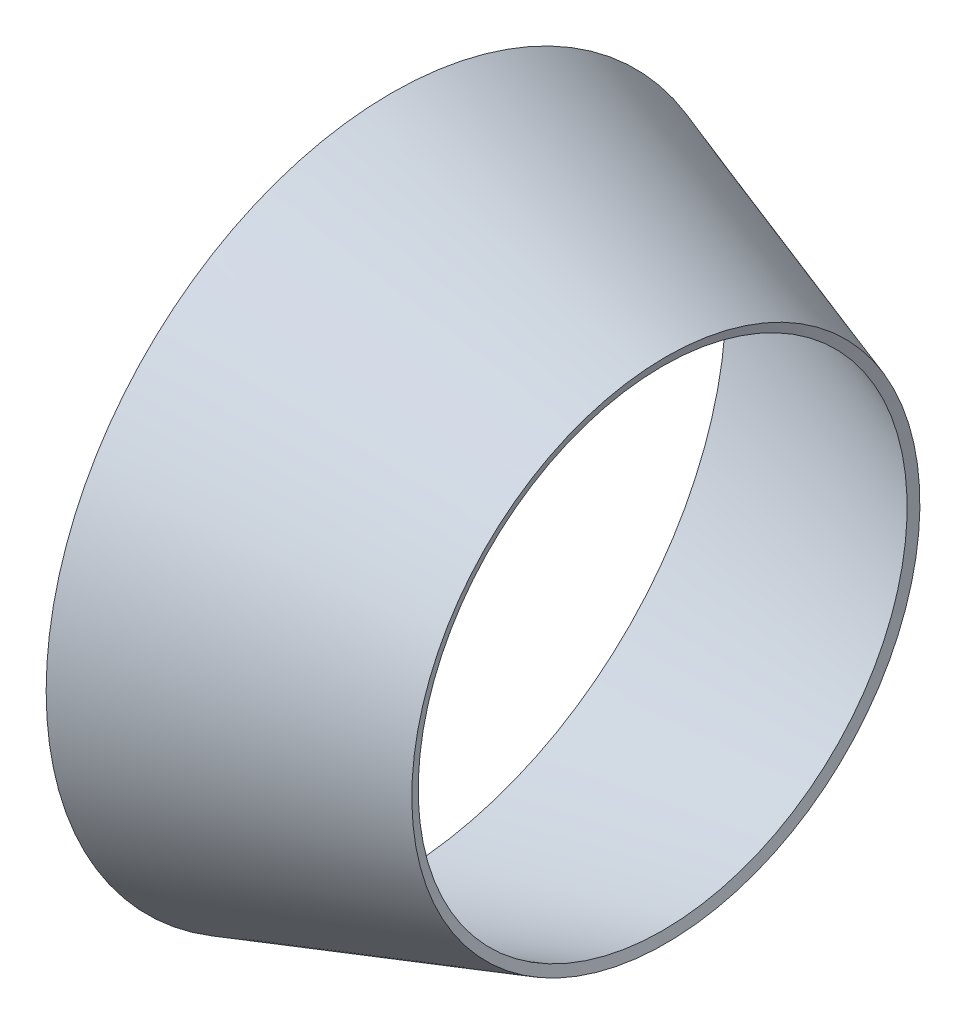
SolidWorks part; units mm, degrees
ref_plane "Front Plane" through (0, 0, 0) normal (0, 0, 1) x (1, 0, 0)
ref_plane "Top Plane" through (0, 0, 0) normal (0, 1, 0) x (1, 0, 0)
ref_plane "Right Plane" through (0, 0, 0) normal (1, 0, 0) x (0, 0, -1)
sketch "Sketch1" plane through (0, 0, 0) normal (0, 0, 1) x (1, 0, 0)
  line L0 (-42.0913, -43.4233) -> (-7.5764, -31.9503)
  line L1 (-42.0913, -44.0429) -> (-42.0913, 44.0429) construction
  line L2 (-7.5764, -31.9503) -> (-7.977, -30.7451)
  line L3 (-7.977, -30.7451) -> (-42.0913, -42.085)
  line L4 (-42.0913, -42.0671) -> (-42.0913, 42.0671) construction
  line L5 (0, 0) -> (-88.1772, 0) construction
  line L6 (-129.4673, 0) -> (-46.8871, 0) construction
  line L7 (-42.0913, -43.4233) -> (-42.0913, -42.085)
  point P6 (-17.2152, -31.5463)
  point P9 (-7.977, -31.9503)
  dimension "D1" = 1.27
revolve "Revolve1" add sketch "Sketch1" angle 360 about L5
